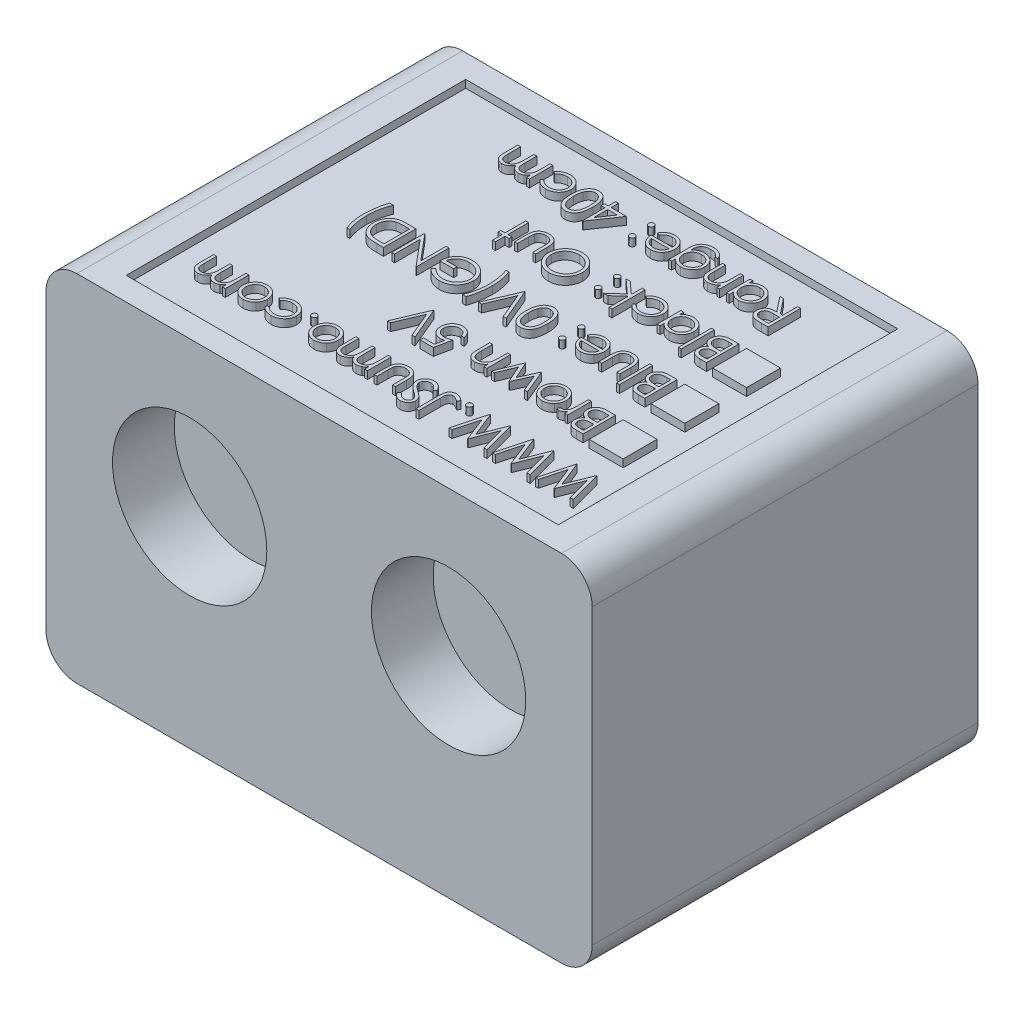
SolidWorks part; units mm, degrees
material "ABS"
ref_plane "Alzado" through (0, 0, 0) normal (0, 0, 1) x (1, 0, 0)
ref_plane "Planta" through (0, 0, 0) normal (0, 1, 0) x (1, 0, 0)
ref_plane "Vista lateral" through (0, 0, 0) normal (1, 0, 0) x (0, 0, -1)
sketch "Croquis1" plane through (0, 0, 0) normal (0, 0, 1) x (1, 0, 0)
  line L1 (7.85, 5.75) -> (-7.85, 5.75)
  line L2 (8.85, 4.75) -> (8.85, -4.75)
  line L3 (7.85, -5.75) -> (-7.85, -5.75)
  line L4 (-8.85, 4.75) -> (-8.85, -4.75)
  line L5 (8.85, 5.75) -> (-8.85, -5.75) construction
  line L6 (8.85, -5.75) -> (-8.85, 5.75) construction
  arc A0 (-7.85, -5.75) -> (-8.85, -4.75) centre (-7.85, -4.75) cw
  arc A1 (8.85, -4.75) -> (7.85, -5.75) centre (7.85, -4.75) cw
  arc A2 (7.85, 5.75) -> (8.85, 4.75) centre (7.85, 4.75) cw
  arc A3 (-7.85, 5.75) -> (-8.85, 4.75) centre (-7.85, 4.75) ccw
  point P0 (0, 0)
  dimension "D3" = 1
  dimension "D1" = 17.7
  dimension "D2" = 11.5
extrude "Saliente-Extruir1" add sketch "Croquis1" along normal blind 12.5
sketch "Croquis2" plane through (0, 0, 12.5) normal (0, 0, 1) x (1, 0, 0)
  line L0 (-4.195, 1.04) -> (4.195, 1.04) construction
  line L1 (0, 0) -> (0, 1.04) construction
  line L2 (-7.85, -5.75) -> (7.85, -5.75) construction
  circle A0 centre (-4.195, 1.04) radius 2.5
  circle A1 centre (4.195, 1.04) radius 2.5
  point P5 (0, 1.04)
  dimension "D1" = 5
  dimension "D2" = 6.79
  dimension "D3" = 8.39
extrude "Cortar-Extruir1" cut sketch "Croquis2" against normal blind 2
sketch "Croquis3" plane through (0, 5.75, 0) normal (0, 1, 0) x (1, 0, 0)
  line L0 (0, 0) -> (0, -12.5) construction
  line L1 (7.85, -12.5) -> (-7.85, -12.5) construction
  line L2 (-7.85, -6.25) -> (7.85, -6.25) construction
  line L3 (-7.85, -12.5) -> (-7.85, 0) construction
  line L4 (7.85, -12.5) -> (7.85, 0) construction
  line L6 (7, -0.75) -> (-7, -0.75)
  line L7 (7, -0.75) -> (7, -11.75)
  line L8 (7, -11.75) -> (-7, -11.75)
  line L9 (-7, -0.75) -> (-7, -11.75)
  line L10 (7, -0.75) -> (-7, -11.75) construction
  line L11 (7, -11.75) -> (-7, -0.75) construction
  point P11 (0, -6.25)
  dimension "D1" = 11
  dimension "D2" = 14
extrude "Cortar-Extruir2" cut sketch "Croquis3" against normal blind 0.25
sketch "Croquis4" plane through (0, 5.5, 0) normal (0, 1, 0) x (1, 0, 0)
  line L0 (7, -9.75) -> (-7, -9.75) construction
  line L1 (7, -11.75) -> (7, -0.75) construction
  line L2 (-7, -0.75) -> (-7, -11.75) construction
  line L3 (7, -7.75) -> (-7, -7.75) construction
  line L4 (7, -3.75) -> (-7, -3.75) construction
  line L5 (7, -11.75) -> (7, -0.75) construction
  line L6 (7, -5.75) -> (-7, -5.75) construction
  line L7 (7, -1.75) -> (-7, -1.75) construction
  line L8 (-7, -0.75) -> (-7, -11.75) construction
  line L9 (-7, -11.75) -> (7, -11.75) construction
  text T0 " WWW.JSumo.com" font "Century Gothic" height in points 4
  text T1 "     Brown 5V" font "Century Gothic" height in points 4
  text T2 "     Blue: 0V(GND)" font "Century Gothic" height in points 4
  text T3 "     Black: Out" font "Century Gothic" height in points 4
  text T4 "     Range: 40cm" font "Century Gothic" height in points 4
  dimension "D1" = 2
  dimension "D2" = 2
  dimension "D3" = 2
  dimension "D4" = 2
  dimension "D5" = 2
extrude "Saliente-Extruir2" add sketch "Croquis4" along normal blind 0.25
sketch "Croquis5" plane through (0, 5.5, 0) normal (0, 1, 0) x (1, 0, 0)
  line L0 (7, -7.75) -> (4, -7.75) construction
  line L1 (7, -11.75) -> (7, -0.75) construction
  line L2 (7, -5.75) -> (4, -5.75) construction
  line L3 (7, -11.75) -> (7, -0.75) construction
  line L4 (7, -3.75) -> (4, -3.75) construction
  line L5 (-7, -11.75) -> (7, -11.75) construction
  line L7 (5.1, -7.75) -> (6.2, -7.75)
  line L8 (5.1, -7.75) -> (5.1, -8.85)
  line L9 (5.1, -8.85) -> (6.2, -8.85)
  line L10 (6.2, -7.75) -> (6.2, -8.85)
  line L11 (6.2, -5.75) -> (5.1, -5.75)
  line L12 (6.2, -5.75) -> (6.2, -6.85)
  line L13 (6.2, -6.85) -> (5.1, -6.85)
  line L14 (5.1, -5.75) -> (5.1, -6.85)
  line L15 (6.2, -3.75) -> (5.1, -3.75)
  line L16 (6.2, -3.75) -> (6.2, -4.85)
  line L17 (6.2, -4.85) -> (5.1, -4.85)
  line L18 (5.1, -3.75) -> (5.1, -4.85)
  point P12 (5.5, -5.75)
  point P13 (5.5, -3.75)
  point P26 (5.1, -6.3)
  dimension "D1" = 3
  dimension "D2" = 4
  dimension "D3" = 2
  dimension "D4" = 2
  dimension "D5" = 1.1
  dimension "D6" = 1.1
  dimension "D7" = 1.9
  dimension "D8" = 1.9
  dimension "D9" = 1.9
extrude "Saliente-Extruir3" add sketch "Croquis5" along normal blind 0.25
sketch "Croquis6" plane through (0, 0, 12.5) normal (0, 0, 1) x (1, 0, 0)
  line L0 (-7.85, -5.75) -> (7.85, -5.75) construction
  circle A0 centre (0, 1.04) radius 0.6834
  dimension "D1" = 6.79
extrude "Saliente-Extruir4" [suppressed] add sketch "Croquis6" along normal blind 300
